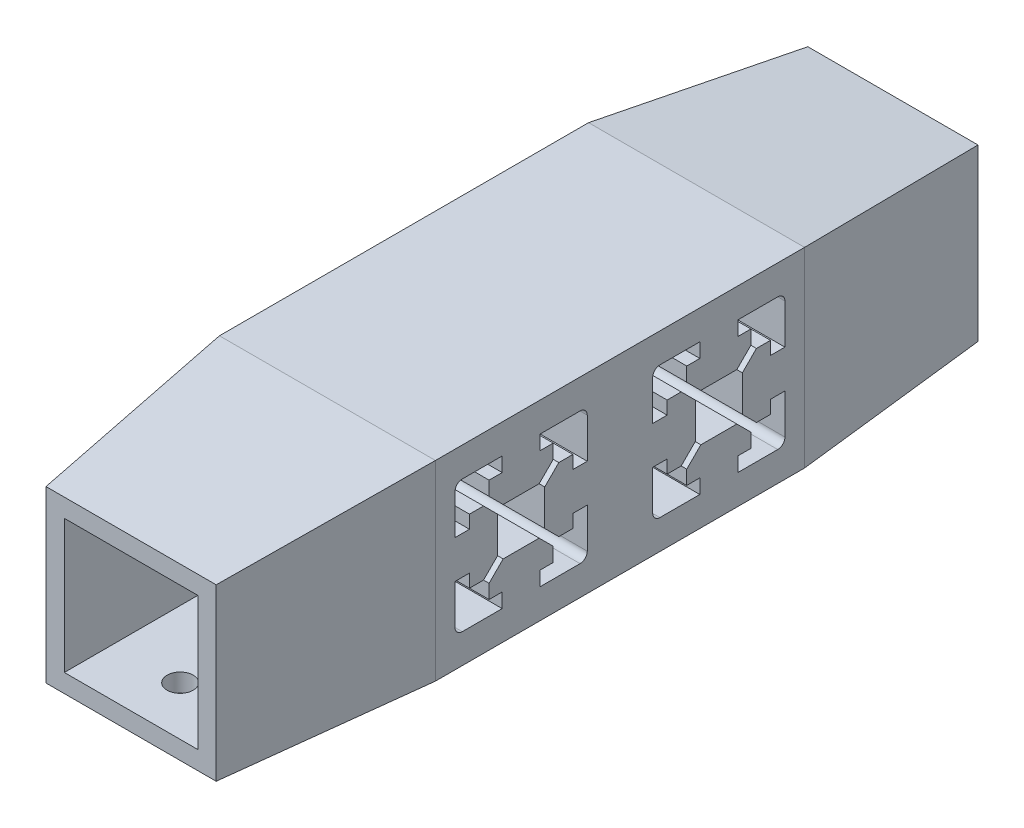
SolidWorks part; units mm, degrees
ref_plane "Front Plane" through (0, 0, 0) normal (0, 0, 1) x (1, 0, 0)
ref_plane "Top Plane" through (0, 0, 0) normal (0, 1, 0) x (1, 0, 0)
ref_plane "Right Plane" through (0, 0, 0) normal (1, 0, 0) x (0, 0, -1)
sketch "Sketch3" plane through (0, 0, 0) normal (1, 0, 0) x (0, 0, -1)
  line L0 (-10.1, 2.9) -> (-10.1, 9)
  line L5 (0, 0) -> (33.3867, 33.3867) construction
  line L6 (2.9, 10.1) -> (9, 10.1)
  line L7 (0, -29.658) -> (0, 39.9767) construction
  line L8 (2.9, 10.1) -> (2.9, 7.9)
  line L9 (2.9, 7.9) -> (4.9, 7.9)
  line L10 (4.9, 7.9) -> (4.9, 5.749)
  line L11 (4.9, 5.749) -> (2.7515, 3.6005)
  line L12 (2.7515, 3.6005) -> (-2.7515, 3.6005)
  line L13 (3.6005, 2.7515) -> (3.6005, -2.7515)
  line L14 (5.749, 4.9) -> (3.6005, 2.7515)
  line L15 (7.9, 4.9) -> (5.749, 4.9)
  line L16 (7.9, 2.9) -> (7.9, 4.9)
  line L17 (10.1, 2.9) -> (7.9, 2.9)
  line L18 (10.1, 2.9) -> (10.1, 9)
  line L19 (-10.1, 2.9) -> (-7.9, 2.9)
  line L20 (-7.9, 2.9) -> (-7.9, 4.9)
  line L21 (-7.9, 4.9) -> (-5.749, 4.9)
  line L22 (-5.749, 4.9) -> (-3.6005, 2.7515)
  line L23 (-3.6005, 2.7515) -> (-3.6005, -2.7515)
  line L24 (-4.9, 5.749) -> (-2.7515, 3.6005)
  line L25 (-4.9, 7.9) -> (-4.9, 5.749)
  line L26 (-2.9, 7.9) -> (-4.9, 7.9)
  line L27 (-2.9, 10.1) -> (-2.9, 7.9)
  line L28 (-2.9, 10.1) -> (-9, 10.1)
  line L29 (-37.4596, 0) -> (35.8917, 0) construction
  line L30 (-2.9, -10.1) -> (-9, -10.1)
  line L31 (-2.9, -10.1) -> (-2.9, -7.9)
  line L32 (-2.9, -7.9) -> (-4.9, -7.9)
  line L33 (-4.9, -7.9) -> (-4.9, -5.749)
  line L34 (-4.9, -5.749) -> (-2.7515, -3.6005)
  line L35 (-5.749, -4.9) -> (-3.6005, -2.7515)
  line L36 (-7.9, -4.9) -> (-5.749, -4.9)
  line L37 (-7.9, -2.9) -> (-7.9, -4.9)
  line L38 (-10.1, -2.9) -> (-7.9, -2.9)
  line L39 (10.1, -2.9) -> (10.1, -9)
  line L40 (10.1, -2.9) -> (7.9, -2.9)
  line L41 (7.9, -2.9) -> (7.9, -4.9)
  line L42 (7.9, -4.9) -> (5.749, -4.9)
  line L43 (5.749, -4.9) -> (3.6005, -2.7515)
  line L44 (2.7515, -3.6005) -> (-2.7515, -3.6005)
  line L45 (4.9, -5.749) -> (2.7515, -3.6005)
  line L46 (4.9, -7.9) -> (4.9, -5.749)
  line L47 (2.9, -7.9) -> (4.9, -7.9)
  line L48 (2.9, -10.1) -> (2.9, -7.9)
  line L49 (2.9, -10.1) -> (9, -10.1)
  line L50 (-10.1, -2.9) -> (-10.1, -9)
  line L52 (-15.1, 14.6) -> (13.1, 14.6)
  line L53 (-15.1, 14.6) -> (-15.1, -14.6)
  line L54 (-15.1, -14.6) -> (13.1, -14.6)
  line L55 (13.1, 14.6) -> (13.1, -14.6)
  arc A0 (9, 10.1) -> (10.1, 9) centre (9, 9) cw
  arc A3 (-9, 10.1) -> (-10.1, 9) centre (-9, 9) ccw
  arc A4 (-9, -10.1) -> (-10.1, -9) centre (-9, -9) cw
  arc A7 (9, -10.1) -> (10.1, -9) centre (9, -9) ccw
  point P0 (0, 0)
  dimension "D3" = 1.1
  dimension "D1" = 45
  dimension "D2" = 20.2
  dimension "D4" = 6.1
  dimension "D5" = 2.2
  dimension "D6" = 2
  dimension "D7" = 2.151
  dimension "D8" = 5.503
  dimension "D9" = 4.5
  dimension "D10" = 4.5
  dimension "D11" = 5
  dimension "D12" = 3
extrude "Boss-Extrude1" add sketch "Sketch3" along normal blind 3 contours L49 A7 L39 L40 L41 L42 L43 L13 L14 L15 L16 L17 L18 A0 L6 L8 L9 L10 L11 L12 L24 L25 L26 L27 L28 A3 L0 L19 L20 L21 L22 L23 L35 L36 L37 L38 L50 A4 L30 L31 L32 L33 L34 L44 L45 L46 L47 L48 | L55 L52 L53 L54 A7 L49 L48 L47 L46 L45 L44 L34 L33 L32 L31 L30 A4 L50 L38 L37 L36 L35 L23 L22 L21 L20 L19 L0 A3 L28 L27 L26 L25 L24 L12 L11 L10 L9 L8 L6 A0 L18 L17 L16 L15 L14 L13 L43 L42 L41 region at (0, 0, 0) region at (0, 14.1941, 1)
extrude "Boss-Extrude2" add sketch "Sketch3<3>" along normal blind 30 from surface starting at face at (3, 0, 1)
sketch "Sketch3<3>" plane through (0, 0, 0) normal (1, 0, 0) x (0, 0, -1) same geometry as "Sketch3"
ref_plane "Plane1" through (0, 0, -43.1) normal (0, 0, -1) x (-1, 0, 0)
sketch "Sketch6" plane through (0, 0, -43.1) normal (0, 0, -1) x (-1, 0, 0)
  line L1 (-29.5, -14.6) -> (-3.5, -14.6)
  line L2 (-29.5, -14.6) -> (-29.5, 11.4)
  line L3 (-29.5, 11.4) -> (-3.5, 11.4)
  line L4 (-3.5, -14.6) -> (-3.5, 11.4)
  line L5 (-16.5, -22.5801) -> (-16.5, 24.7352) construction
  line L6 (-26.7, 8.6) -> (-6.3, 8.6)
  line L7 (-26.7, 8.6) -> (-26.7, -11.8)
  line L8 (-26.7, -11.8) -> (-6.3, -11.8)
  line L9 (-6.3, 8.6) -> (-6.3, -11.8)
  line L10 (-33, -14.6) -> (0, -14.6) construction
  point P4 (-16.5, -14.6)
  point P5 (-16.5, -14.6)
  point P12 (0, 0)
  point P15 (-28.5083, -14.6)
  dimension "D1" = 20.4
  dimension "D2" = 20.4
  dimension "D3" = 2.8
  dimension "D4" = 2.8
  dimension "D5" = 2.8
  dimension "D6" = 2.8
loft "Loft2" add section face at (16.5, 0, -13.1) section "Sketch6" connector at (33, 14.6, -13.1) connector at (29.5, 11.4, -43.1)
extrude "Cut-Extrude2" cut sketch "Sketch6<4>" against normal blind 30 contours L8 L5 L6 L7 | L5 L8 L9 L6 region at (21.6, -1.6, -43.1) region at (11.4, -1.6, -43.1)
sketch "Sketch6<4>" plane through (0, 0, -43.1) normal (0, 0, -1) x (-1, 0, 0) same geometry as "Sketch6"
sketch "Sketch8" plane through (0, -11.8, 0) normal (0, 1, 0) x (1, 0, 0)
  line L0 (16.5, 43.1) -> (16.5, 13.1) construction
  line L1 (29.5, 43.1) -> (3.5, 43.1) construction
  line L2 (33, 13.1) -> (0, 13.1) construction
  circle A0 centre (16.5, 35.6) radius 2
  circle A1 centre (16.5, 20.6) radius 2
  dimension "D3" = 4
  dimension "D1" = 7.5
  dimension "D2" = 15
extrude "Cut-Extrude3" cut sketch "Sketch8" against normal blind 30
mirror "Mirror2" about plane through (3, 0, 15.1) normal (0, 0, -1) of bodies 106
